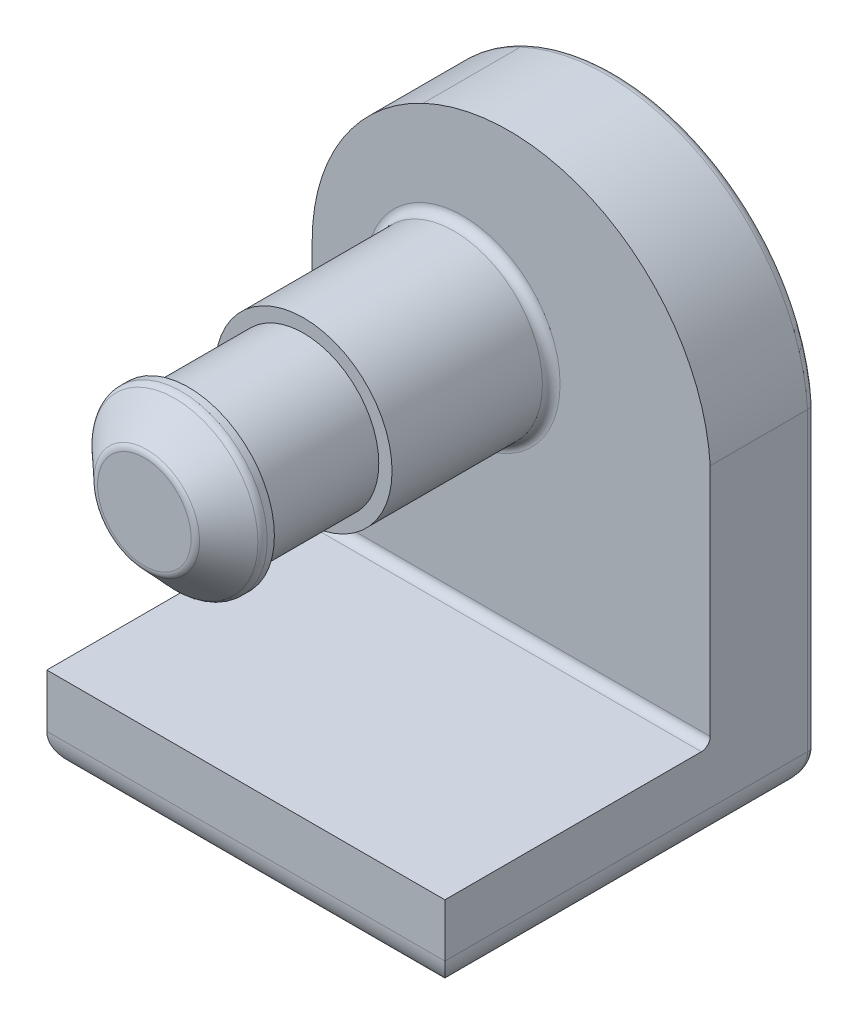
SolidWorks part; units mm, degrees
ref_plane "Front Plane" through (0, 0, 0) normal (0, 0, 1) x (1, 0, 0)
ref_plane "Top Plane" through (0, 0, 0) normal (0, 1, 0) x (1, 0, 0)
ref_plane "Right Plane" through (0, 0, 0) normal (1, 0, 0) x (0, 0, -1)
sketch "Sketch1" plane through (0, 0, 0) normal (0, 0, 1) x (1, 0, 0)
  line L0 (0, 0) -> (10.3566, 0) construction
  line L4 (-3.4059, 0) -> (-3.4059, -5.4)
  line L5 (-3.4059, -5.4) -> (5.5941, -5.4)
  line L6 (5.5941, 0.1007) -> (5.5941, -5.4)
  arc A1 (-3.4059, 0) -> (-0.8981, 3.9521) centre (0.9621, 0) cw
  arc A2 (-0.8981, 3.9521) -> (5.5941, 0.1007) centre (1.0434, -0.1728) cw
  dimension "D2" = 5.4
  dimension "D1" = 9
extrude "Boss-Extrude1" add sketch "Sketch1" along normal blind 2.4
sketch "Sketch3" plane through (0, 0, 0) normal (0, 0, 1) x (1, 0, 0)
  line L0 (0, 0) -> (6.1619, 0) construction
  line L1 (0, 0) -> (6.0229, 10.432) construction
  circle A0 centre (0, 0) radius 2
extrude "Boss-Extrude2" add sketch "Sketch3" along normal blind 6
sketch "Sketch4" plane through (0, 0, 0) normal (0, 0, 1) x (1, 0, 0)
  line L1 (-3.4059, -5.4) -> (5.5941, -5.4)
  line L2 (-3.4059, -5.4) -> (-3.4059, -7.4)
  line L3 (-3.4059, -7.4) -> (5.5941, -7.4)
  line L4 (5.5941, -5.4) -> (5.5941, -7.4)
  dimension "D1" = 2
  dimension "D2" = 9
extrude "Boss-Extrude3" add sketch "Sketch4" along normal blind 8.4
fillet "Fillet1" radius 0.8 4 edges at (-3.4059, -7.4, 4.2) (1.0941, -7.4, 8.4) (5.5941, -7.4, 4.2) (1.0941, -7.4, 0)
fillet "Fillet2" radius 0.2 7 edges at (-3.1716, -7.1657, 0.2343) (5.3598, -7.1657, 0.2343) (5.5941, -3.2497, 0) (3.3694, 3.7481, 0) (-2.726, 2.3403, 0) (-3.4059, -3.3, 0) (1.0941, -5.4, 2.4)
fillet "Fillet3" radius 0.2 1 edges at (-2, 0, 2.4)
ref_plane "Plane1" through (0, 0, 6) normal (0, 0, 1) x (1, 0, 0)
sketch "Sketch5" plane through (0, 0, 6) normal (0, 0, 1) x (1, 0, 0)
  circle A0 centre (0, 0) radius 1.7
extrude "Boss-Extrude4" add sketch "Sketch5" along normal blind 2.6
ref_plane "Plane2" through (0, 0, 8.6) normal (0, 0, 1) x (1, 0, 0)
sketch "Sketch6" plane through (0, 0, 8.6) normal (0, 0, 1) x (1, 0, 0)
  circle A0 centre (0, 0) radius 1.94
extrude "Boss-Extrude5" add sketch "Sketch6" along normal blind 1
chamfer "Chamfer1" distance 0.75 angle 47 1 edges at (1.94, 0, 9.6) first distance on face at (1.94, 0, 9.6)
fillet "Fillet4" radius 0.2 2 edges at (1.1357, 0, 9.6) (1.94, 0, 8.85)
ref_plane "Plane3" through (0, -8, 0) normal (0, -1, 0) x (-1, 0, 0)
sketch "Sketch7" plane through (0, -8, 0) normal (0, -1, 0) x (-1, 0, 0)
  line L0 (2.6059, -0.8) -> (-4.7941, -7.6) construction
  line L1 (2.6059, -7.6) -> (-4.7941, -0.8) construction
  line L2 (-1.0941, -4.2) -> (-4.7941, -4.2) construction
  line L3 (-1.7817, -6.316) -> (0.7059, -5.5078)
  line L4 (0.7059, -5.5078) -> (0.7059, -2.8922)
  line L5 (0.7059, -2.8922) -> (-1.7817, -2.084)
  line L6 (-1.7817, -2.084) -> (-3.319, -4.2)
  line L7 (-3.319, -4.2) -> (-1.7817, -6.316)
  line L8 (-4.7941, -0.8) -> (-4.7941, -7.6) construction
  circle A0 centre (-1.0941, -4.2) radius 1.8 construction
extrude "Boss-Extrude6" add sketch "Sketch7" against normal up to next
scale "Scale1" scale about centroid uniform scaling yes scale factor 1.15
